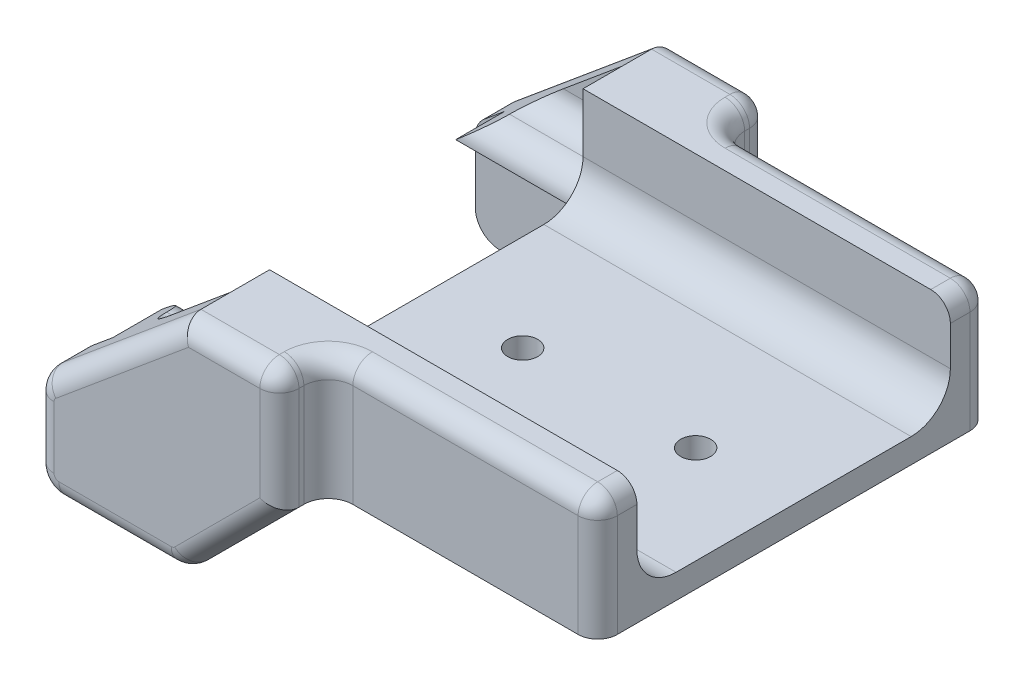
SolidWorks part; units mm, degrees
material "ABS"
ref_plane "Front Plane" through (0, 0, 0) normal (0, 0, 1) x (1, 0, 0)
ref_plane "Top Plane" through (0, 0, 0) normal (0, 1, 0) x (1, 0, 0)
ref_plane "Right Plane" through (0, 0, 0) normal (1, 0, 0) x (0, 0, -1)
sketch "Sketch1" plane through (0, 0, 0) normal (0, 1, 0) x (1, 0, 0)
  line L1 (-23.8125, -25.4) -> (23.8125, -25.4)
  line L2 (-23.8125, -25.4) -> (-23.8125, 25.4)
  line L3 (-23.8125, 25.4) -> (23.8125, 25.4)
  line L4 (23.8125, -25.4) -> (23.8125, 25.4)
  line L5 (-23.8125, -25.4) -> (23.8125, 25.4) construction
  line L6 (-23.8125, 25.4) -> (23.8125, -25.4) construction
  point P0 (0, 0)
  dimension "D1" = 50.8
  dimension "D2" = 47.625
extrude "Boss-Extrude1" add sketch "Sketch1" along normal blind 3.175
sketch "Sketch2" plane through (0, 3.175, 0) normal (0, 1, 0) x (1, 0, 0)
  line L0 (-64.6286, 0) -> (64.6286, 0) construction
  line L1 (23.8125, -25.4) -> (23.8125, 25.4) construction
  circle A0 centre (11.1125, 0) radius 1.9431
  circle A1 centre (-11.3157, 0) radius 1.9431
  dimension "D1" = 22.4282
  dimension "D2" = 12.7
  dimension "D3" = 3.8862
extrude "Cut-Extrude1" cut sketch "Sketch2" against normal through all
sketch "Sketch3" plane through (23.8125, 0, 0) normal (1, 0, 0) x (0, 0, -1)
  line L1 (-25.4, 3.175) -> (-20.32, 3.175)
  line L2 (-25.4, 3.175) -> (-25.4, 15.875)
  line L3 (-25.4, 15.875) -> (-20.32, 15.875)
  line L4 (-20.32, 3.175) -> (-20.32, 15.875)
  line L5 (25.4, 3.175) -> (20.32, 3.175)
  line L6 (25.4, 3.175) -> (25.4, 15.875)
  line L7 (25.4, 15.875) -> (20.32, 15.875)
  line L8 (20.32, 3.175) -> (20.32, 15.875)
  line L9 (25.4, 3.175) -> (25.4, 0) construction
  dimension "D1" = 12.7
  dimension "D2" = 5.08
extrude "Boss-Extrude2" add sketch "Sketch3" against normal up to vertex (47.625 mm away) up to point (-23.8125, 3.175, 25.4)
fillet "Fillet1" radius 5.08 2 edges at (0, 3.175, -20.32) (0, 3.175, 20.32)
sketch "Sketch5" plane through (0, 0, -25.4) normal (0, 0, -1) x (-1, 0, 0)
  line L0 (11.1125, 15.875) -> (23.8125, 15.875)
  line L1 (23.8125, 15.875) -> (-23.8125, 15.875) construction
  line L2 (23.8125, 15.875) -> (42.8625, 0)
  line L3 (67.2731, 0) -> (-67.2731, 0) construction
  line L4 (42.8625, 0) -> (42.8625, -12.7)
  line L5 (42.8625, -12.7) -> (23.8125, -12.7)
  line L6 (23.8125, -12.7) -> (11.1125, 0)
  line L7 (11.1125, 0) -> (11.1125, 15.875)
  line L8 (23.8125, 15.875) -> (23.8125, 0) construction
  dimension "D1" = 19.05
  dimension "D2" = 12.7
  dimension "D3" = 12.7
  dimension "D4" = 45
extrude "Boss-Extrude4" add sketch "Sketch5" along normal blind 6.35
fillet "Fillet4" radius 3.175 4 edges at (-23.8125, -12.7, -28.575) (-42.8625, -12.7, -28.575) (-42.8625, 0, -28.575) (-11.1125, 7.9375, -25.4)
sketch "Sketch6" plane through (0, 0, 25.4) normal (0, 0, 1) x (1, 0, 0)
  line L0 (-11.1125, 15.875) -> (-23.8125, 15.875)
  line L1 (-23.8125, 15.875) -> (23.8125, 15.875) construction
  line L2 (-23.8125, 15.875) -> (-42.8625, 0)
  line L3 (67.2731, 0) -> (-67.2731, 0) construction
  line L4 (-42.8625, 0) -> (-42.8625, -12.7)
  line L5 (-42.8625, -12.7) -> (-23.8125, -12.7)
  line L6 (-23.8125, -12.7) -> (-11.1125, 0)
  line L7 (-11.1125, 0) -> (-22.8826, -11.7701) construction
  line L8 (-11.1125, 0) -> (-11.1125, 15.875)
  line L9 (-41.7201, 0.952) -> (-23.8125, 15.875) construction
  line L10 (-25.1276, -12.7) -> (-39.6875, -12.7) construction
  line L11 (-23.8125, 15.875) -> (-23.8125, 0) construction
  point P17 (-11.1125, 7.9375)
  dimension "D1" = 12.7
extrude "Boss-Extrude5" add sketch "Sketch6" along normal blind 6.35
fillet "Fillet6" radius 3.175 4 edges at (-23.8125, -12.7, 28.575) (-42.8625, -12.7, 28.575) (-42.8625, 0, 28.575) (-11.1125, 7.9375, 25.4)
sketch "Sketch7" plane through (0, 0, -25.4) normal (0, 0, 1) x (1, 0, 0)
  line L0 (-23.8125, 15.875) -> (-23.8125, 0) construction
  line L1 (-23.8125, 3.175) -> (-39.0525, 3.175)
  line L2 (-23.8125, 3.175) -> (-23.8125, 6.35)
  line L3 (-23.8125, 6.35) -> (-35.2425, 6.35)
  line L5 (-39.0525, 3.175) -> (-35.2425, 6.35)
  line L10 (-23.8125, 15.875) -> (-41.7201, 0.952) construction
  dimension "D1" = 3.175
extrude "Boss-Extrude6" add sketch "Sketch7" along normal blind 6.35
fillet "Fillet8" radius 3.175 2 edges at (-29.5275, 6.35, -19.05) (-29.5275, 6.35, -25.4)
mirror "Mirror5" about plane through (0, 0, 0) normal (0, 0, 1) of "Boss-Extrude6"
fillet "Fillet9" radius 3.175 2 edges at (-29.5275, 6.35, 25.4) (-29.5275, 6.35, 19.05)
fillet "Fillet10" radius 2.54 18 edges at (-41.9326, -11.7701, 31.75) (-42.8625, -5.506, 31.75) (-42.5627, -0.1404, 31.75) (-32.7663, 8.4135, 31.75) (-17.4625, 15.875, 31.75) (-11.1125, 7.9375, 31.75) (-16.9975, -5.885, 31.75) (-23.9126, -12.4583, 31.75) (-32.4076, -12.7, 31.75) (-11.1125, 7.9375, -31.75) (-17.4625, 15.875, -31.75) (-32.7663, 8.4135, -31.75) (-42.5627, -0.1404, -31.75) (-42.8625, -5.506, -31.75) (-41.9326, -11.7701, -31.75) (-32.4076, -12.7, -31.75) (-23.9126, -12.4583, -31.75) (-16.9975, -5.885, -31.75)
fillet "Fillet11" radius 2.54 10 edges at (-11.8564, 15.1311, 31.0061) (-11.1125, 15.875, 28.8925) (-10.1826, 15.875, 26.3299) (-11.8564, 15.1311, -31.0061) (-11.1125, 15.875, -28.8925) (-10.1826, 15.875, -26.3299) (23.8125, 7.9375, -25.4) (23.8125, 7.9375, 25.4) (7.9375, 15.875, 25.4) (7.9375, 15.875, -25.4)
fillet "Fillet12" radius 2.54 4 edges at (23.0686, 15.1311, -24.6561) (23.0686, 15.1311, 24.6561) (23.8125, 15.875, -21.59) (23.8125, 15.875, 21.59)
